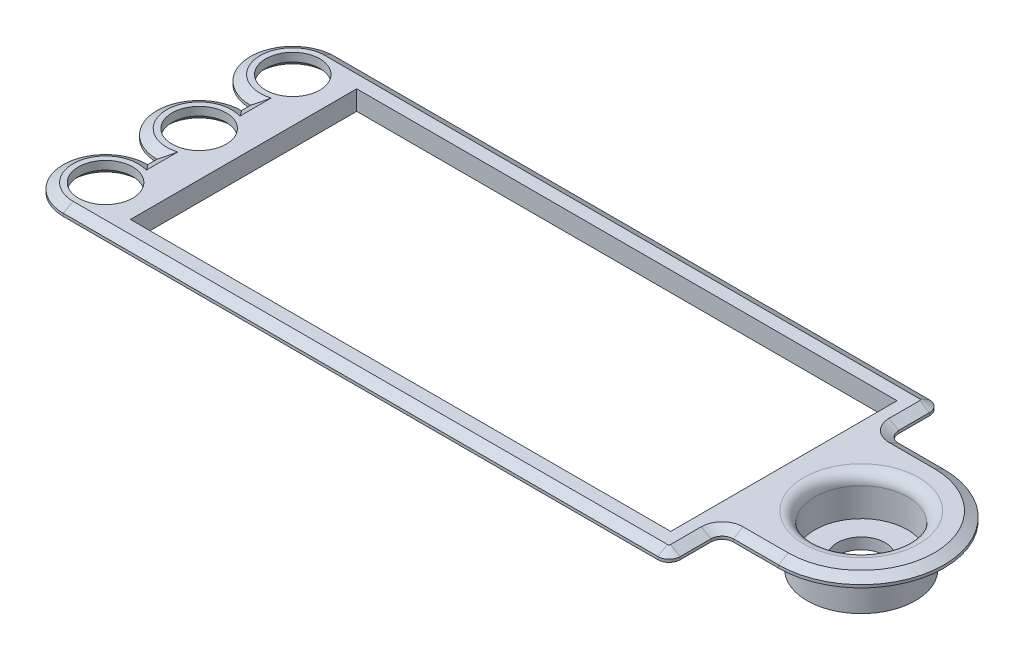
SolidWorks part; units mm, degrees
ref_plane "Спереди" through (0, 0, 0) normal (0, 0, 1) x (1, 0, 0)
ref_plane "Сверху" through (0, 0, 0) normal (0, 1, 0) x (1, 0, 0)
ref_plane "Справа" through (0, 0, 0) normal (1, 0, 0) x (0, 0, -1)
sketch "Эскиз1" plane through (0, 0, 0) normal (0, 1, 0) x (1, 0, 0)
  line L1 (-71, 24.3) -> (71, 24.3)
  line L2 (-71, 24.3) -> (-71, -24.3)
  line L3 (-71, -24.3) -> (71, -24.3)
  line L4 (71, 24.3) -> (71, -24.3)
  line L5 (-71, 24.3) -> (71, -24.3) construction
  line L6 (-71, -24.3) -> (71, 24.3) construction
  point P0 (0, 0)
  dimension "D1" = 142
  dimension "D2" = 48.6
extrude "Бобышка-Вытянуть1" add sketch "Эскиз1" along normal blind 1.5
sketch "Эскиз2" plane through (0, 0, 0) normal (0, -1, 0) x (1, 0, 0)
  line L0 (-54.35, 20.25) -> (42.35, 20.25)
  line L1 (-55.7, 21.6) -> (43.7, 21.6) construction
  line L2 (-55.7, 21.6) -> (-55.7, -21.6) construction
  line L3 (-55.7, -21.6) -> (43.7, -21.6) construction
  line L4 (43.7, 21.6) -> (43.7, -21.6) construction
  line L5 (42.35, 20.25) -> (42.35, -20.25)
  line L6 (-54.35, -20.25) -> (42.35, -20.25)
  line L7 (-54.35, 20.25) -> (-54.35, -20.25)
  circle A0 centre (-62.3, 16.75) radius 5.5 construction
  circle A1 centre (-62.3, 0) radius 5.5 construction
  circle A2 centre (-62.3, -16.75) radius 5.5 construction
  circle A3 centre (-62.3, -16.75) radius 4.85
  circle A4 centre (-62.3, 0) radius 4.85
  circle A5 centre (-62.3, 16.75) radius 4.85
  dimension "D1" = 1.35
  dimension "D2" = 0.65
  dimension "D3" = 0.65
  dimension "D4" = 0.65
extrude "Вырез-Вытянуть1" cut sketch "Эскиз2" against normal up to surface (1.5 mm away) up to face at (0, 1.5, 0)
sketch "Эскиз3" plane through (0, 0, 0) normal (0, -1, 0) x (1, 0, 0)
  line L0 (-54.35, -20.25) -> (42.35, -20.25) construction
  line L1 (42.35, -20.25) -> (42.35, 20.25) construction
  line L2 (42.35, 20.25) -> (-54.35, 20.25) construction
  line L3 (-54.35, 20.25) -> (-54.35, -20.25) construction
  line L4 (-54.35, -20.25) -> (42.35, -20.25)
  line L5 (42.35, -20.25) -> (42.35, 20.25)
  line L6 (42.35, 20.25) -> (-54.35, 20.25)
  line L7 (-54.35, 20.25) -> (-54.35, -20.25)
  line L8 (-55.35, -21.25) -> (43.35, -21.25)
  line L9 (43.35, -21.25) -> (43.35, 21.25)
  line L10 (43.35, 21.25) -> (-55.35, 21.25)
  line L11 (-55.35, 21.25) -> (-55.35, -21.25)
  dimension "D1" = 1
extrude "Бобышка-Вытянуть2" add sketch "Эскиз3" along normal blind 2
sketch "Эскиз4" plane through (0, 0, 0) normal (0, -1, 0) x (1, 0, 0)
  circle A0 centre (-62.3, -16.75) radius 4.85 construction
  circle A1 centre (-62.3, 0) radius 4.85 construction
  circle A2 centre (-62.3, 16.75) radius 4.85 construction
  circle A3 centre (-62.3, -16.75) radius 4.85
  circle A4 centre (-62.3, 0) radius 4.85
  circle A5 centre (-62.3, 16.75) radius 4.85
  circle A6 centre (-62.3, -16.75) radius 5.85
  circle A7 centre (-62.3, 0) radius 5.85
  circle A8 centre (-62.3, 16.75) radius 5.85
  dimension "D1" = 1
extrude "Бобышка-Вытянуть3" add sketch "Эскиз4" along normal blind 2
chamfer "Фаска1" distance 2 angle 45 3 edges at (-62.3, -2, -21.6) (-62.3, -2, -4.85) (-62.3, -2, 11.9)
sketch "Эскиз6" plane through (0, 0, 0) normal (0, -1, 0) x (1, 0, 0)
  circle A0 centre (56.2, 0) radius 10 construction
  circle A1 centre (56.2, 0) radius 8.3
  dimension "D1" = 1.7
extrude "Вырез-Вытянуть2" cut sketch "Эскиз6" against normal up to surface (1.5 mm away) up to face at (-62.3, 1.5, -11.9)
sketch "Эскиз8" plane through (0, 0, 0) normal (0, -1, 0) x (1, 0, 0)
  circle A0 centre (56.2, 0) radius 8.3 construction
  circle A1 centre (56.2, 0) radius 8.3
  circle A2 centre (56.2, 0) radius 9.7
  dimension "D1" = 1.4
extrude "Бобышка-Вытянуть4" add sketch "Эскиз8" along normal blind 7.6
sketch "Эскиз9" plane through (0, -7.6, 0) normal (0, -1, 0) x (1, 0, 0)
  circle A0 centre (56.2, 0) radius 9.7 construction
  circle A1 centre (56.2, 0) radius 9.7
extrude "Бобышка-Вытянуть5" add sketch "Эскиз9" against normal blind 2
sketch "Эскиз10" plane through (0, -7.6, 0) normal (0, -1, 0) x (1, 0, 0)
  circle A0 centre (56.2, 0) radius 4.3
  dimension "D1" = 8.6
extrude "Вырез-Вытянуть3" cut sketch "Эскиз10" against normal up to surface (2 mm away) up to face at (56.2, -5.6, -8.3)
sketch "Эскиз11" plane through (0, -7.6, 0) normal (0, -1, 0) x (1, 0, 0)
  line L0 (57.2, 6.15) -> (57.2, 6.4) construction
  line L1 (54.8, 6.8) -> (57.6, 6.8)
  line L2 (54.8, 6.8) -> (54.8, 5.5)
  line L3 (54.8, 5.5) -> (57.6, 5.5)
  line L4 (57.6, 6.8) -> (57.6, 5.5)
  line L5 (55.2, 6.4) -> (55.2, 6.15) construction
  line L6 (55.2, 5.9) -> (57.2, 5.9) construction
  line L7 (55.2, 6.4) -> (57.2, 6.4) construction
  dimension "D1" = 0.4
  dimension "D2" = 0.4
  dimension "D3" = 0.4
  dimension "D4" = 0.4
extrude "Вырез-Вытянуть4" cut sketch "Эскиз11" against normal up to surface (2 mm away) up to face at (56.2, -5.6, -4.3)
sketch "Эскиз12" plane through (0, 1.5, 0) normal (0, 1, 0) x (1, 0, 0)
  line L0 (-62.3, 24.3) -> (-62.3, -24.3) construction
  line L1 (71, 24.3) -> (-71, 24.3) construction
  line L2 (-71, -24.3) -> (71, -24.3) construction
  line L3 (-62.3, 24.3) -> (-71, 24.3)
  line L4 (-71, 24.3) -> (-71, -24.3)
  line L5 (-71, -24.3) -> (-62.3, -24.3)
  line L6 (-62.3, -9.2) -> (-62.3, -7.55)
  line L7 (-62.3, 7.55) -> (-62.3, 9.1762)
  circle A0 centre (-62.3, 16.75) radius 4.85 construction
  circle A1 centre (-62.3, -16.75) radius 4.85 construction
  circle A2 centre (-62.3, 0) radius 4.85 construction
  arc A3 (-62.3, 21.6) -> (-62.3, 11.9) centre (-62.3, 16.75) ccw
  arc A4 (-62.3, -11.9) -> (-62.3, -21.6) centre (-62.3, -16.75) ccw
  arc A5 (-62.3, 4.85) -> (-62.3, -4.85) centre (-62.3, 0) ccw
  arc A6 (-62.3, -24.3) -> (-62.3, -9.2) centre (-62.3, -16.75) cw
  arc A7 (-69.85, 0) -> (-62.3, -7.55) centre (-62.3, 0) ccw
  arc A8 (-69.85, 0) -> (-62.3, 7.55) centre (-62.3, 0) cw
  arc A9 (-69.85, 16.15) -> (-62.3, 9.1762) centre (-62.3, 16.75) ccw
  arc A10 (-69.85, 16.15) -> (-62.3, 24.3238) centre (-62.3, 16.75) cw
  line M13 (-71, 24.3) -> (-71, -24.3)
  line M14 (-71, -24.3) -> (71, -24.3)
sketch "Эскиз13" plane through (0, 1.5, 0) normal (0, 1, 0) x (1, 0, 0)
  line L0 (46.1, 24.3) -> (46.1, -24.3) construction
  line L1 (71, 24.3) -> (-71, 24.3) construction
  line L2 (-71, -24.3) -> (71, -24.3) construction
  line L3 (71, -24.3) -> (71, 24.3) construction
  line L4 (56.2, 14.8) -> (46.1, 14.8)
  line L5 (56.2, -14.8) -> (46.1, -14.8)
  line L6 (46.1, -14.8) -> (46.1, -24.3)
  line L7 (46.1, -24.3) -> (71, -24.3)
  line L8 (71, -24.3) -> (71, 24.3)
  line L9 (71, 24.3) -> (46.1, 24.3)
  line L10 (46.1, 24.3) -> (46.1, 14.8)
  line L11 (46.1, 14.8) -> (49.3914, 14.2407)
  line L12 (42.35, 20.25) -> (42.35, -20.25) construction
  arc A1 (71, 0) -> (56.2, 14.8) centre (56.2, 0) ccw
  arc A2 (71, 0) -> (56.2, -14.8) centre (56.2, 0) cw
  line M12 (-71, -24.3) -> (71, -24.3)
  line M13 (71, -24.3) -> (71, 24.3)
  line M14 (71, 24.3) -> (-71, 24.3)
  dimension "D1" = 3.75
extrude "Вырез-Вытянуть6" cut sketch "Эскиз13" against normal up to surface (1.5 mm away) contours A1 L8 L10 L4 M14 | A2 L5 L6 M13 M12 region at (60.0659, 1.5, 18.2145) region at (60.0659, 1.5, -18.2145) up to face at (-62.3, 0, 22.6)
fillet "Скругление1" radius 2 1 edges at (56.2, 1.5, 8.3)
fillet "Скругление2" radius 2 4 edges at (46.1, 0.75, -14.8) (46.1, 0.75, 14.8) (46.1, 0.75, 24.3) (46.1, 0.75, -24.3)
extrude "Вырез-Вытянуть8" cut sketch "Эскиз12" against normal up to surface (1.5 mm away) contours A9 A10 L3 A6 L6 A7 A8 L7 M13 M14 region at (-68.4386, 1.5, -21.9848) up to face at (56.2, 0, 9.7)
chamfer "Фаска2" distance 1 angle 60 16 edges at (-69.85, 1.5, 16.75) (-9.1, 1.5, 24.3) (45.5142, 1.5, 23.7142) (46.1, 1.5, 19.55) (46.6858, 1.5, 15.3858) (52.15, 1.5, 14.8) (71, 1.5, 0) (52.15, 1.5, -14.8) (46.6858, 1.5, -15.3858) (46.1, 1.5, -19.55) (45.5142, 1.5, -23.7142) (-62.3, 1.5, 8.375) (-69.85, 1.5, 0) (-62.3, 1.5, -8.3631) (-69.8679, 1.5, -16.4498) (-9.4, 1.5, -24.3) first distance on face at (-66.075, 0.75, 16.75) first distance on face at (-9.1, 0.75, 24.3) first distance on face at (45.3071, 0.75, 23.5071) first distance on face at (46.1, 0.75, 19.55) first distance on face at (46.8929, 0.75, 15.5929) first distance on face at (52.15, 0.75, 14.8) first distance on face at (63.6, 0.75, 0) first distance on face at (52.15, 0.75, -14.8) first distance on face at (46.8929, 0.75, -15.5929) first distance on face at (46.1, 0.75, -19.55) first distance on face at (45.3071, 0.75, -23.5071) first distance on face at (-62.3, 0.75, 8.375) first distance on face at (-66.075, 0.75, 0) first distance on face at (-62.3, 0.75, -8.3631) first distance on face at (-66.2339, 0.75, -16.5939) first distance on face at (-9.4, 0.75, -24.3)
